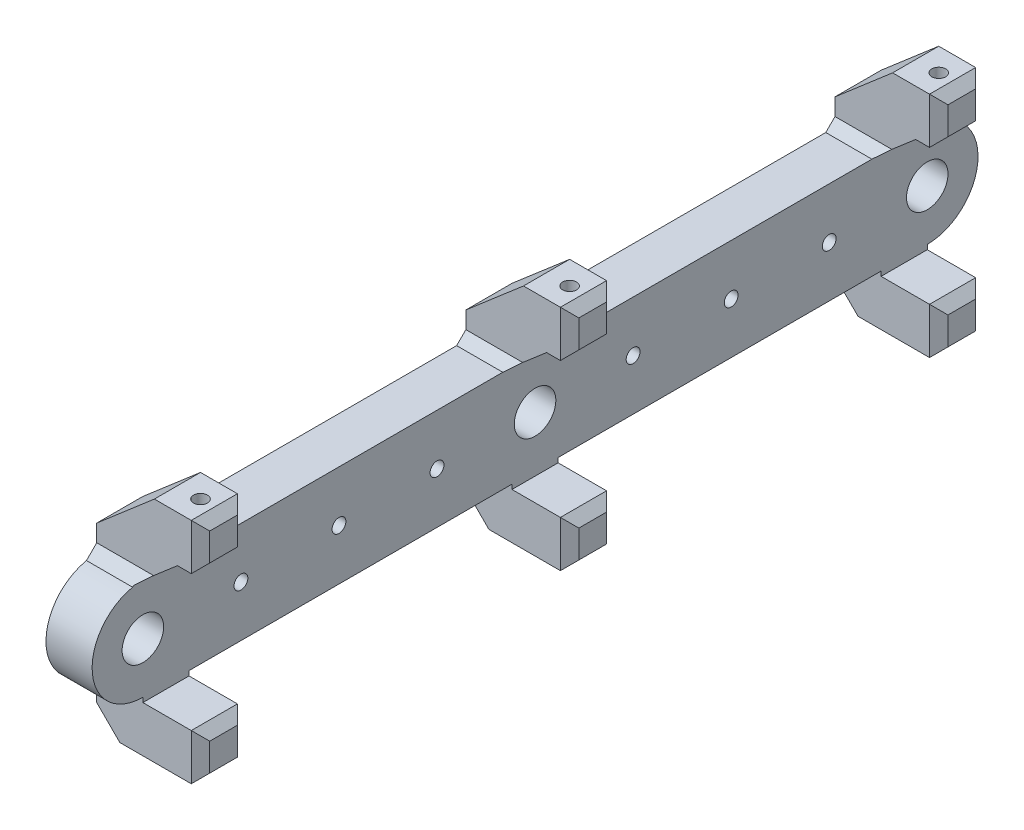
SolidWorks part; units mm, degrees
ref_plane "Front Plane" through (0, 0, 0) normal (0, 0, 1) x (1, 0, 0)
ref_plane "Top Plane" through (0, 0, 0) normal (0, 1, 0) x (1, 0, 0)
ref_plane "Right Plane" through (0, 0, 0) normal (1, 0, 0) x (0, 0, -1)
sketch "Sketch1" plane through (0, 0, 0) normal (1, 0, 0) x (0, 0, -1)
  line L0 (0, 0) -> (170, 0) construction
  line L1 (0, 11) -> (170, 11)
  line L2 (0, -11) -> (170, -11)
  circle A0 centre (0, 0) radius 4.5
  arc A1 (0, 11) -> (0, -11) centre (0, 0) ccw
  arc A2 (170, -11) -> (170, 11) centre (170, 0) ccw
  circle A3 centre (0, 0) radius 35 construction
  circle A4 centre (85, 0) radius 35 construction
  circle A5 centre (170, 0) radius 35 construction
  circle A6 centre (85, 0) radius 4.5
  circle A7 centre (170, 0) radius 4.5
  point P3 (85, 0)
  dimension "D1" = 85
  dimension "D3" = 70
  dimension "D4" = 9
  dimension "D2" = 85
extrude "Boss-Extrude1" add sketch "Sketch1" along normal blind 10 contours A0 | A6 | A7 | L1 A2 L2 A1 region at (0, 0, 0) region at (0, 0, -85) region at (0, 0, -170)
sketch "Sketch3" plane through (0, 0, 0) normal (-1, 0, 0) x (0, 0, 1)
  line L0 (-63.75, 0) -> (-42.5, 0) construction
  line L1 (-42.5, 0) -> (-21.25, 0) construction
  line L2 (-85, 0) -> (-63.75, 0) construction
  line L3 (-21.25, 0) -> (0, 0) construction
  line L4 (-170, 0) -> (-148.75, 0) construction
  line L5 (-148.75, 0) -> (-127.5, 0) construction
  line L6 (-127.5, 0) -> (-106.25, 0) construction
  line L7 (-106.25, 0) -> (-85, 0) construction
  circle A2 centre (-42.5, 0) radius 1.5
  circle A3 centre (-63.75, 0) radius 1.5
  circle A4 centre (-21.25, 0) radius 1.5
  circle A5 centre (-148.75, 0) radius 1.5
  circle A6 centre (-127.5, 0) radius 1.5
  circle A7 centre (-106.25, 0) radius 1.5
  dimension "D1" = 3
extrude "Cut-Extrude1" cut sketch "Sketch3" against normal through all
sketch "Sketch6" plane through (10, 0, 0) normal (1, 0, 0) x (0, 0, -1)
  circle A0 centre (106.25, 0) radius 10.4
  circle A1 centre (127.5, 0) radius 10.4
  circle A2 centre (148.75, 0) radius 10.4
  circle A3 centre (85, 0) radius 10.5
  circle A4 centre (170, 0) radius 10.5
  circle A5 centre (63.75, 0) radius 10.5
  circle A6 centre (42.5, 0) radius 10.5
  circle A7 centre (21.25, -0.085) radius 10.5
sketch "Sketch7" plane through (0, 0, 0) normal (0, 0, 1) x (1, 0, 0)
  line L0 (10, -10.5) -> (10, 10.5) construction
  line L1 (0, 11) -> (0, 16.6971)
  line L3 (0, 11) -> (10, 11)
  line L4 (22.4897, 27.4454) -> (12.4897, 27.4454)
  line L5 (5.2275, 15.015) -> (5.4467, 43.2136) construction
  line L6 (22.4897, 17.4454) -> (17.4897, 17.4454)
  line L7 (12.4897, 27.4454) -> (0, 16.6971)
  line L8 (17.4897, 17.4454) -> (10, 11)
  line L9 (22.4897, 17.4454) -> (22.4897, 27.4454)
  dimension "D1" = 10
  dimension "D2" = 10
extrude "Boss-Extrude2" add sketch "Sketch7" against normal blind 10 separate body
ref_point "Point1"
ref_point "Point2"
ref_axis "Axis1" through (10, 0, -85) along (-1, 0, 0)
ref_plane "Plane1" through (0, 0, -85) normal (0, 0, -1) x (-1, 0, 0)
pattern_linear "LPattern1" count 3 spacing 80 along (0, 0, -1) of "Boss-Extrude2"
combine bodies "Combine1" operation type add bodies to combine 109 103 108 106
chamfer "Chamfer2" distance 2 angle 45 6 edges at (5, 11, -10) (5, 11, 0) (5, 11, -80) (5, 11, -90) (5, 11, -170) (5, 11, -160)
sketch "Sketch8" plane through (0, -11, 0) normal (0, -1, 0) x (-1, 0, 0)
  line L0 (-10, 0) -> (0, 0)
  line L1 (0, 0) -> (0, 10)
  line L2 (0, 10) -> (-10, 10)
  line L3 (-10, 10) -> (-10, 0)
extrude "Boss-Extrude3" add sketch "Sketch8" along normal blind 1
sketch "Sketch10" plane through (10, 0, 0) normal (1, 0, 0) x (0, 0, -1)
  line L0 (10, -12) -> (10, -22)
  line L1 (10, -22) -> (0, -22)
  line L2 (0, -22) -> (0, -12)
  line L3 (0, -12) -> (10, -12)
extrude "Boss-Extrude5" add sketch "Sketch10" along normal up to surface (12.4897 mm away) and the other way blind 10 up to face at (22.4897, 22.4454, -5)
chamfer "Chamfer3" distance 5 angle 45 1 edges at (0, -22, -5)
pattern_linear "LPattern3" count 3 spacing 80 along (0, 0, -1) of "Boss-Extrude5", "Boss-Extrude3", "Chamfer3"
sketch "Sketch12" plane through (0, 27.4454, 0) normal (0, 1, 0) x (1, 0, 0)
  line L0 (17.4897, 10) -> (17.4897, 0) construction
  line L1 (22.4897, 10) -> (12.4897, 10) construction
  line L2 (17.4897, 90) -> (17.4897, 80) construction
  line L3 (22.4897, 90) -> (12.4897, 90) construction
  line L4 (22.4897, 80) -> (12.4897, 80) construction
  line L5 (17.4897, 170) -> (17.4897, 160) construction
  line L6 (22.4897, 170) -> (12.4897, 170) construction
  line L7 (22.4897, 160) -> (12.4897, 160) construction
  circle A0 centre (17.4897, 5) radius 1.5
  circle A1 centre (17.4897, 165) radius 1.5
  circle A2 centre (17.4897, 85) radius 1.5
extrude "Cut-Extrude2" cut sketch "Sketch12" against normal blind 7
sketch "Sketch13" plane through (0, -22, 0) normal (0, -1, 0) x (-1, 0, 0)
  line L0 (-17.4897, 170) -> (-17.4897, 160) construction
  line L1 (-17.4897, 90) -> (-17.4897, 80) construction
  line L2 (-17.4897, 10) -> (-17.4897, 0) construction
  circle A0 centre (-17.4897, 165) radius 1.5
  circle A1 centre (-17.4897, 85) radius 1.5
  circle A2 centre (-17.4897, 5) radius 1.5
extrude "Cut-Extrude3" cut sketch "Sketch13" against normal blind 7
chamfer "Chamfer4" distance 2 angle 45 24 edges at (22.4897, 27.4454, -165) (22.4897, 22.4454, -170) (22.4897, 17.4454, -165) (22.4897, 22.4454, -160) (22.4897, -22, -5) (22.4897, -17, 0) (22.4897, -12, -5) (22.4897, -17, -10) (22.4897, -22, -85) (22.4897, -17, -80) (22.4897, -12, -85) (22.4897, -17, -90) (22.4897, -22, -165) (22.4897, -17, -160) (22.4897, -12, -165) (22.4897, -17, -170) (22.4897, 17.4454, -85) (22.4897, 22.4454, -80) (22.4897, 27.4454, -85) (22.4897, 22.4454, -90) (22.4897, 22.4454, -10) (22.4897, 17.4454, -5) (22.4897, 22.4454, 0) (22.4897, 27.4454, -5)
